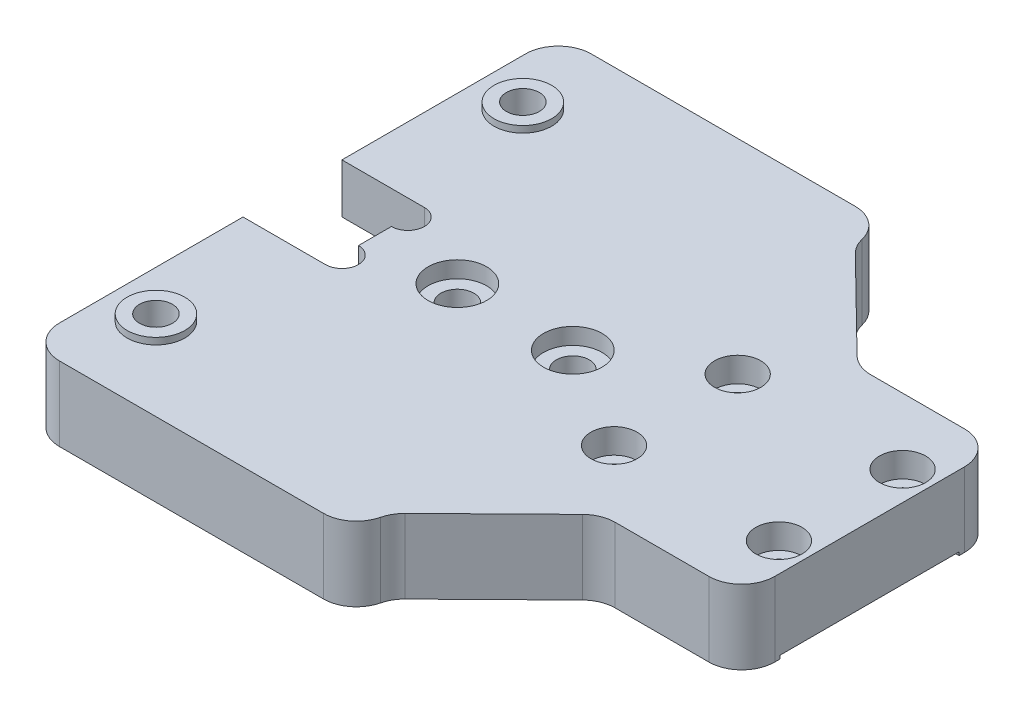
SolidWorks part; units mm, degrees
ref_plane "Front Plane" through (0, 0, 0) normal (0, 0, 1) x (1, 0, 0)
ref_plane "Top Plane" through (0, 0, 0) normal (0, 1, 0) x (1, 0, 0)
ref_plane "Right Plane" through (0, 0, 0) normal (1, 0, 0) x (0, 0, -1)
sketch "Sketch1" plane through (0, 0, 0) normal (0, 1, 0) x (1, 0, 0)
  line L0 (0, 0) -> (21.5, 0) construction
  line L5 (21.5, 20) -> (21.5, -20)
  line L6 (21.5, -20) -> (-20.5, -32.5)
  line L7 (-20.5, -32.5) -> (-84.5, -32.5)
  line L8 (-84.5, -32.5) -> (-84.5, 32.5)
  line L11 (-84.5, 32.5) -> (-20.5, 32.5)
  line L12 (-20.5, 32.5) -> (21.5, 20)
  circle A0 centre (0, 0) radius 12
  point P7 (21.5, 0)
  dimension "D4" = 24
  dimension "D6" = 9.5
  dimension "D1" = 40
  dimension "D2" = 106
  dimension "D3" = 65
  dimension "D5" = 64
extrude "Boss-Extrude1" add sketch "Sketch1" along normal mid plane 9
sketch "Sketch2" plane through (0, 4.5, 0) normal (0, 1, 0) x (1, 0, 0)
  line L0 (0, 0) -> (-19.5, 0) construction
  line L1 (-15.5, -15.5) -> (15.5, -15.5) construction
  line L2 (-15.5, -15.5) -> (-15.5, 15.5) construction
  line L3 (-15.5, 15.5) -> (15.5, 15.5) construction
  line L4 (15.5, -15.5) -> (15.5, 15.5) construction
  line L5 (-15.5, -15.5) -> (15.5, 15.5) construction
  line L6 (-15.5, 15.5) -> (15.5, -15.5) construction
  line L7 (-19.5, 27.5) -> (-19.5, -27.5) construction
  line L9 (-84.5, 32.5) -> (-84.5, -32.5) construction
  circle A0 centre (15.5, 15.5) radius 1.7
  circle A1 centre (-15.5, 15.5) radius 1.7
  circle A2 centre (-15.5, -15.5) radius 1.7
  circle A3 centre (15.5, -15.5) radius 1.7
  circle A4 centre (-19.5, 27.5) radius 1.7
  circle A5 centre (-19.5, -27.5) radius 1.7
  point P0 (0, 0)
  dimension "D2" = 3.4
  dimension "D1" = 31
  dimension "D3" = 55
  dimension "D4" = 65
extrude "Cut-Extrude1" cut sketch "Sketch2" against normal through all
fillet "Fillet1" radius 4 6 edges at (-84.5, 0, -32.5) (-84.5, 0, 32.5) (-20.5, 0, 32.5) (21.5, 0, 20) (-20.5, 0, -32.5) (21.5, 0, -20)
sketch "Sketch5" plane through (0, 4.5, 0) normal (0, 1, 0) x (1, 0, 0)
  line L0 (-24.5, 32.5) -> (-24.5, 10)
  line L1 (-21.0826, 32.5) -> (-80.5, 32.5) construction
  line L2 (-80.5, -32.5) -> (-21.0826, -32.5) construction
  line L3 (-84.5, 28.5) -> (-84.5, -28.5) construction
  line L4 (-24.5, 32.5) -> (26.912, 32.5)
  line L5 (-24.5, -10) -> (-29.5, -10) construction
  line L6 (-24.5, -10) -> (-24.5, 10) construction
  line L7 (-24.5, 10) -> (-29.5, 10) construction
  line L8 (-29.5, -10) -> (-29.5, 10) construction
  line L9 (26.912, 32.5) -> (26.912, -32.5)
  line L11 (-24.5, -32.5) -> (26.912, -32.5)
  line L12 (-24.5, 10) -> (-24.5, -10) construction
  line L13 (-24.5, -10) -> (-24.5, -32.5)
  line L14 (-29.5, 0) -> (0, 0) construction
  line L15 (-24.5, 10) -> (-24.5, -10)
  dimension "D1" = 60
  dimension "D2" = 20
  dimension "D3" = 5
extrude "Cut-Extrude4" cut sketch "Sketch5" against normal through all
fillet "Fillet3" radius 4 2 edges at (-24.5, 0, -32.5) (-24.5, 0, 32.5)
sketch "Sketch6" plane through (0, -4.5, 0) normal (0, -1, 0) x (1, 0, 0)
  line L0 (-48, -7.5) -> (-48, 7.5) construction
  line L3 (-48, -7.5) -> (-28, -7.5) construction
  line L4 (-28, -7.5) -> (-28, 7.5) construction
  line L5 (-28, 7.5) -> (-48, 7.5) construction
  line L6 (-24.5, -28.5) -> (-24.5, 28.5) construction
  line L7 (-28.5, -32.5) -> (-80.5, -32.5) construction
  circle A0 centre (-48, -7.5) radius 1.5
  circle A1 centre (-48, 7.5) radius 1.5
  circle A2 centre (-28, 7.5) radius 1.5
  circle A3 centre (-28, -7.5) radius 1.5
  dimension "D3" = 3.5
  dimension "D5" = 3
  dimension "D1" = 15
  dimension "D2" = 20
  dimension "D4" = 25
extrude "Cut-Extrude5" cut sketch "Sketch6" against normal blind 41
sketch "Sketch7" plane through (0, 4.5, 0) normal (0, 1, 0) x (1, 0, 0)
  line L0 (-84.5, 28.5) -> (-84.5, -28.5) construction
  line L1 (-84.5, 10) -> (-54.5, 10)
  line L2 (-84.5, 10) -> (-84.5, -10)
  line L3 (-84.5, -10) -> (-54.5, -10)
  line L4 (-54.5, 10) -> (-54.5, -10)
  line L5 (-28.5, 32.5) -> (-80.5, 32.5) construction
  dimension "D1" = 20
  dimension "D2" = 22.5
  dimension "D3" = 30
extrude "Cut-Extrude6" cut sketch "Sketch7" against normal blind 3 from offset 6 offset against normal yes
sketch "Sketch8" plane through (0, 4.5, 0) normal (0, 1, 0) x (1, 0, 0)
  line L0 (-84.5, 28.5) -> (-84.5, -28.5) construction
  line L1 (-84.5, 15.5) -> (-24.5, 15.5)
  line L2 (-84.5, 15.5) -> (-84.5, 32.5)
  line L3 (-84.5, 32.5) -> (-24.5, 32.5)
  line L4 (-24.5, 15.5) -> (-24.5, 32.5)
  line L5 (-84.5, 28.5) -> (-84.5, -28.5) construction
  line L7 (-24.5, 28.5) -> (-24.5, -28.5) construction
  line L8 (-28.5, 32.5) -> (-80.5, 32.5) construction
  line L9 (-84.5, 0) -> (-24.5, 0) construction
  line L11 (-84.5, -32.5) -> (-24.5, -32.5)
  line L12 (-24.5, -15.5) -> (-24.5, -32.5)
  line L13 (-84.5, -15.5) -> (-24.5, -15.5)
  line L14 (-84.5, -15.5) -> (-84.5, -32.5)
  dimension "D1" = 17
extrude "Cut-Extrude8" cut sketch "Sketch8" against normal blind 9
fillet "Fillet6" radius 4 2 edges at (-24.5, 0, -15.5) (-24.5, 0, 15.5)
sketch "Sketch9" plane through (0, 4.5, 0) normal (0, 1, 0) x (1, 0, 0)
  line L0 (-84.5, 15.5) -> (-28.5, 15.5) construction
  line L1 (-54.5, 10) -> (-94.5, 10)
  line L2 (-54.5, 10) -> (-54.5, 32.25)
  line L3 (-54.5, 32.25) -> (-94.5, 32.25)
  line L4 (-94.5, 10) -> (-94.5, 32.25)
  line L5 (-24.5, 11.5) -> (-24.5, -11.5) construction
  line L7 (-24.5, 0) -> (-84.5, 0) construction
  line L9 (-54.5, -32.25) -> (-94.5, -32.25)
  line L10 (-94.5, -10) -> (-94.5, -32.25)
  line L11 (-54.5, -10) -> (-94.5, -10)
  line L12 (-54.5, -10) -> (-54.5, -32.25)
  line L13 (-84.5, 15.5) -> (-84.5, -15.5) construction
  dimension "D1" = 30
  dimension "D2" = 40
  dimension "D3" = 22.25
  dimension "D4" = 5.5
extrude "Boss-Extrude3" add sketch "Sketch9" against normal blind 9
fillet "Fillet7" radius 4 4 edges at (-94.5, 0, -32.25) (-54.5, 0, -32.25) (-54.5, 0, 32.25) (-94.5, 0, 32.25)
sketch "Sketch13" plane through (0, 4.5, 0) normal (0, 1, 0) x (1, 0, 0)
  line L0 (-84.5, 0) -> (-24.5, 0) construction
  line L1 (-84.5, 10) -> (-84.5, -10) construction
  line L2 (-24.5, 11.5) -> (-24.5, -11.5) construction
  line L3 (-58.5, 32.25) -> (-90.5, 32.25) construction
  line L4 (-94.5, 28.25) -> (-94.5, 10) construction
  circle A0 centre (-88.81, 22.25) radius 3.5
  circle A1 centre (-88.81, -22.25) radius 3.5
  dimension "D1" = 7
  dimension "D2" = 10
  dimension "D3" = 5.69
extrude "Boss-Extrude5" add sketch "Sketch13" along normal blind 0.8
sketch "Sketch10" plane through (0, 4.5, 0) normal (0, 1, 0) x (1, 0, 0)
  line L0 (-94.5, -10) -> (-94.5, -28.25) construction
  line L1 (-90.5, -32.25) -> (-58.5, -32.25) construction
  line L2 (-24.5, 0) -> (-84.5, 0) construction
  line L3 (-24.5, 11.5) -> (-24.5, -11.5) construction
  line L4 (-84.5, 10) -> (-84.5, -10) construction
  circle A0 centre (-88.81, -22.25) radius 2
  circle A1 centre (-88.81, 22.25) radius 2
  dimension "D2" = 10
  dimension "D3" = 4
  dimension "D1" = 5.69
extrude "Cut-Extrude9" cut sketch "Sketch10" against normal blind 9 and the other way blind 2
sketch "Sketch11" plane through (0, 4.5, 0) normal (0, 1, 0) x (1, 0, 0)
  line L0 (-54.5, 28.25) -> (-41.5, 15.5)
  line L1 (-54.5, 15.5) -> (-54.5, 28.25) construction
  line L2 (-54.5, 15.5) -> (-28.5, 15.5) construction
  line L3 (-54.5, -28.25) -> (-41.5, -15.5)
  line L4 (-28.5, -15.5) -> (-54.5, -15.5) construction
  line L5 (-54.5, -28.25) -> (-54.5, -15.5) construction
  line L6 (-54.5, 28.25) -> (-54.5, 15.5)
  line L7 (-54.5, 15.5) -> (-41.5, 15.5)
  line L8 (-54.5, -28.25) -> (-54.5, -15.5)
  line L9 (-54.5, -15.5) -> (-41.5, -15.5)
  arc A0 (-58.5, -32.25) -> (-54.5, -28.25) centre (-58.5, -28.25) ccw construction
  arc A1 (-54.5, 28.25) -> (-58.5, 32.25) centre (-58.5, 28.25) ccw construction
extrude "Boss-Extrude4" add sketch "Sketch11" against normal blind 9
sketch "Sketch14" plane through (0, -1.5, 0) normal (0, -1, 0) x (1, 0, 0)
  line L0 (-84.5, 0) -> (-24.5, 0) construction
  line L1 (-84.5, -10) -> (-84.5, 10) construction
  line L2 (-24.5, -11.5) -> (-24.5, 11.5) construction
  line L3 (-54.5, 10) -> (-54.5, -10) construction
  circle A0 centre (-74.5, 0) radius 2
  circle A1 centre (-60.5, 0) radius 2
  dimension "D1" = 4
  dimension "D2" = 4
  dimension "D3" = 6
  dimension "D4" = 14
extrude "Cut-Extrude10" cut sketch "Sketch14" against normal blind 16
sketch "Sketch15" plane through (0, -4.5, 0) normal (0, -1, 0) x (1, 0, 0)
  line L0 (-24.5, -11.5) -> (-24.5, 11.5) construction
  line L1 (-24.5, 10.85) -> (-32, 10.85)
  line L2 (-24.5, 10.85) -> (-24.5, -10.85)
  line L3 (-24.5, -10.85) -> (-32, -10.85)
  line L4 (-32, 10.85) -> (-32, -10.85)
  line L5 (-28.5, 15.5) -> (-41.5, 15.5) construction
  line L6 (-38, 15.5) -> (-38, -15.5) construction
  line L7 (-41.5, -15.5) -> (-28.5, -15.5) construction
  line L8 (-51.5, 10.85) -> (-44, 10.85)
  line L9 (-51.5, 10.85) -> (-51.5, -10.85)
  line L10 (-44, 10.85) -> (-44, -10.85)
  line L11 (-51.5, -10.85) -> (-44, -10.85)
  dimension "D1" = 7.5
  dimension "D2" = 21.7
  dimension "D3" = 4.65
  dimension "D4" = 13.5
extrude "Cut-Extrude11" cut sketch "Sketch15" against normal blind 0.4
chamfer "Chamfer2" distance 0.4 angle 45 2 edges at (-32, -4.1, 0) (-44, -4.1, 0)
chamfer "Chamfer3" distance 0.6 angle 45 1 edges at (-51.5, -4.1, 0)
sketch "Sketch16" plane through (-84.5, 0, 0) normal (-1, 0, 0) x (0, 0, 1)
  line L0 (-10, 4.5) -> (10, 4.5) construction
  line L1 (-10, 4.5) -> (-6, 4.5)
  line L2 (-10, 4.5) -> (-10, -1.5)
  line L3 (-10, -1.5) -> (-6, -1.5)
  line L4 (-6, 4.5) -> (-6, -1.5)
  line L5 (-10, 4.5) -> (-10, -1.5) construction
  line L6 (-10, -1.5) -> (10, -1.5) construction
  line L8 (10, 4.5) -> (6, 4.5)
  line L9 (10, 4.5) -> (10, -1.5)
  line L10 (10, -1.5) -> (6, -1.5)
  line L11 (6, 4.5) -> (6, -1.5)
  line L12 (10, -1.5) -> (10, 4.5) construction
  dimension "D1" = 4
extrude "Boss-Extrude6" add sketch "Sketch16" along normal blind 10
sketch "Sketch17" plane through (0, 4.5, 0) normal (0, 1, 0) x (1, 0, 0)
  line L0 (-84.5, 0) -> (-24.5, 0) construction
  line L1 (-84.5, 6) -> (-84.5, -6) construction
  line L2 (-24.5, 11.5) -> (-24.5, -11.5) construction
  line L3 (-94.5, 6) -> (-84.5, 6) construction
  circle A0 centre (-84.5, 4) radius 2
  circle A1 centre (-84.5, -4) radius 2
  dimension "D1" = 4
extrude "Cut-Extrude12" cut sketch "Sketch17" against normal blind 12.4
sketch "Sketch18" plane through (0, 4.5, 0) normal (0, 1, 0) x (1, 0, 0)
  line L0 (-60.5, 0) -> (-74.5, 0) construction
  line L1 (-90.5, -32.25) -> (-58.5, -32.25) construction
  line L2 (-84.5, 2) -> (-84.5, -2) construction
  circle A0 centre (-74.5, 0) radius 3.55
  circle A1 centre (-60.5, 0) radius 3.55
  dimension "D1" = 7.1
  dimension "D2" = 14
  dimension "D3" = 32.25
  dimension "D4" = 10
extrude "Cut-Extrude13" cut sketch "Sketch18" against normal blind 2
sketch "Sketch19" plane through (0, 4.5, 0) normal (0, 1, 0) x (1, 0, 0)
  line L0 (-48, 7.5) -> (-48, -7.5) construction
  line L1 (-48, -7.5) -> (-28, -7.5) construction
  line L2 (-28, -7.5) -> (-28, 7.5) construction
  line L3 (-28, 7.5) -> (-48, 7.5) construction
  line L4 (-41.5, 15.5) -> (-28.5, 15.5) construction
  line L5 (-24.5, 11.5) -> (-24.5, -11.5) construction
  circle A0 centre (-48, 7.5) radius 2.8
  circle A1 centre (-28, 7.5) radius 2.8
  circle A2 centre (-48, -7.5) radius 2.8
  circle A3 centre (-28, -7.5) radius 2.8
  dimension "D3" = 5.6
  dimension "D1" = 15
  dimension "D2" = 20
  dimension "D4" = 8
  dimension "D5" = 3.5
extrude "Cut-Extrude14" cut sketch "Sketch19" against normal blind 3
sketch "Sketch20" plane through (0, -4.5, 0) normal (0, -1, 0) x (1, 0, 0)
  line L0 (-32, 10.85) -> (-32, -10.85) construction
  line L1 (-24.5, 10.85) -> (-32, 10.85) construction
  line L2 (-31.6, -10.85) -> (-24.5, -10.85) construction
  line L3 (-51.3, -10.85) -> (-51.3, 10.85) construction
  line L4 (-44, -10.85) -> (-44, 10.85) construction
  line L5 (-44, 10.85) -> (-51.3, 10.85) construction
  line L6 (-51.3, -10.85) -> (-44, -10.85) construction
  line L11 (-50.9, 10.85) -> (-50.9, -10.85) construction
  line L12 (-51.3, -6.85) -> (-50.9, -6.85)
  line L14 (-51.3, -10.85) -> (-50.9, -10.85)
  line L15 (-50.9, -6.85) -> (-50.9, -10.85)
  line L16 (-44.4, -10.85) -> (-44.4, 10.85) construction
  line L17 (-44, -6.85) -> (-44.4, -6.85)
  line L19 (-44, -10.85) -> (-44.4, -10.85)
  line L20 (-44.4, -6.85) -> (-44.4, -10.85)
  line L22 (-51.3, 6.85) -> (-50.9, 6.85)
  line L24 (-51.3, 10.85) -> (-50.9, 10.85)
  line L25 (-50.9, 6.85) -> (-50.9, 10.85)
  line L26 (-44, 6.85) -> (-44.4, 6.85)
  line L28 (-44, 10.85) -> (-44.4, 10.85)
  line L29 (-44.4, 6.85) -> (-44.4, 10.85)
  circle A0 centre (-32, 8.85) radius 2
  circle A1 centre (-32, -8.85) radius 2
  arc A2 (-51.3, 10.85) -> (-51.3, 6.85) centre (-51.3, 8.85) ccw
  arc A3 (-51.3, -6.85) -> (-51.3, -10.85) centre (-51.3, -8.85) ccw
  arc A4 (-44, -10.85) -> (-44, -6.85) centre (-44, -8.85) ccw
  arc A5 (-44, 6.85) -> (-44, 10.85) centre (-44, 8.85) ccw
  dimension "D1" = 4
extrude "Cut-Extrude15" cut sketch "Sketch20" against normal blind 0.4
fillet "Fillet8" radius 4 4 edges at (-54.5, 0, -28.25) (-41.5, 0, -15.5) (-41.5, 0, 15.5) (-54.5, 0, 28.25)
sketch "Sketch21" plane through (0, -4.5, 0) normal (0, -1, 0) x (1, 0, 0)
  line L0 (-94.5, 10) -> (-54.5, 10) construction
  line L1 (-54.5, 10) -> (-54.5, -10) construction
  line L2 (-54.5, -10) -> (-94.5, -10) construction
  line L3 (-54.5, 10) -> (-54.5, -10) construction
  circle A0 centre (-56.5, 10) radius 2
  circle A1 centre (-56.5, -10) radius 2
  dimension "D1" = 4
extrude "Cut-Extrude16" cut sketch "Sketch21" against normal blind 3
